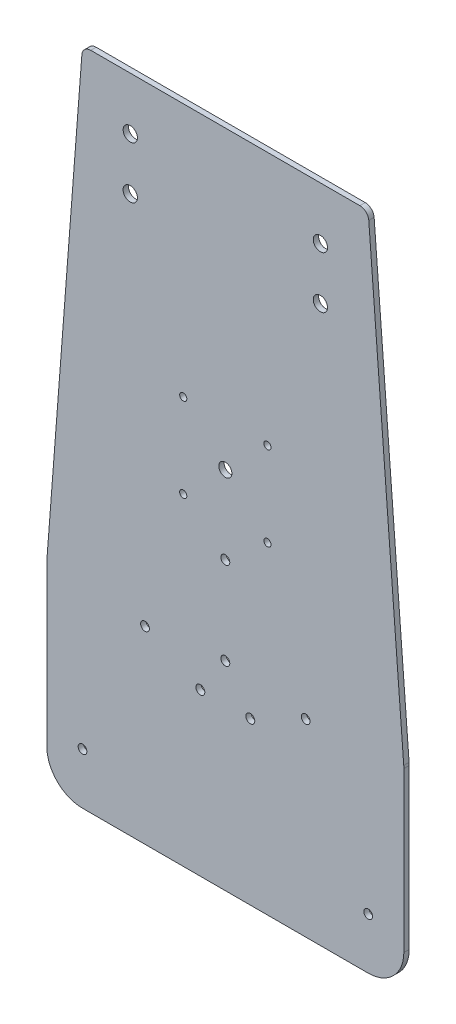
SolidWorks part; units mm, degrees
ref_plane "Alzado" through (0, 0, 0) normal (0, 0, 1) x (1, 0, 0)
ref_plane "Planta" through (0, 0, 0) normal (0, 1, 0) x (1, 0, 0)
ref_plane "Vista lateral" through (0, 0, 0) normal (1, 0, 0) x (0, 0, -1)
sketch "Croquis1" plane through (0, 0, 0) normal (0, 0, 1) x (1, 0, 0)
  line L0 (0, -28.2) -> (0, -108.2) construction
  line L1 (-23.57, -23.57) -> (23.57, -23.57) construction
  line L2 (-23.57, -23.57) -> (-23.57, 23.57) construction
  line L3 (-23.57, 23.57) -> (23.57, 23.57) construction
  line L4 (23.57, -23.57) -> (23.57, 23.57) construction
  line L5 (-23.57, -23.57) -> (23.57, 23.57) construction
  line L6 (-23.57, 23.57) -> (23.57, -23.57) construction
  line L7 (-28.2, -28.2) -> (28.2, -28.2) construction
  line L8 (-28.2, -28.2) -> (-28.2, 28.2) construction
  line L9 (-28.2, 28.2) -> (28.2, 28.2) construction
  line L10 (28.2, -28.2) -> (28.2, 28.2) construction
  line L11 (-28.2, -28.2) -> (28.2, 28.2) construction
  line L12 (-28.2, 28.2) -> (28.2, -28.2) construction
  line L13 (0, -28.2) -> (30.1, -28.2) construction
  line L14 (0, -108.2) -> (0, -169.2) construction
  line L15 (-30.1, -108.2) -> (30.1, -108.2) construction
  line L16 (-30.1, -108.2) -> (-30.1, -28.2) construction
  line L17 (-30.1, -28.2) -> (30.1, -28.2) construction
  line L18 (30.1, -108.2) -> (30.1, -28.2) construction
  line L19 (-30.1, -108.2) -> (30.1, -28.2) construction
  line L20 (-30.1, -28.2) -> (30.1, -108.2) construction
  line L21 (-14, -108.7) -> (-14, -113.7) construction
  line L22 (-221.5898, -108.7) -> (221.5898, -108.7) construction
  line L23 (-221.5898, -108.7) -> (-221.5898, -168.7) construction
  line L24 (-221.5898, -168.7) -> (221.5898, -168.7) construction
  line L25 (221.5898, -108.7) -> (221.5898, -168.7) construction
  line L26 (-221.5898, -108.7) -> (221.5898, -168.7) construction
  line L27 (-221.5898, -168.7) -> (221.5898, -108.7) construction
  line L28 (-221.5898, -122.2) -> (221.5898, -122.2) construction
  line L29 (-221.5898, -138.7) -> (221.5898, -138.7) construction
  line L30 (0, -169.2) -> (0, -204.2) construction
  line L31 (-100, -204.2) -> (100, -204.2)
  line L32 (100, -204.2) -> (100, -94.2)
  line L33 (100, -94.2) -> (80, 165.8)
  line L34 (80, 165.8) -> (-80, 165.8)
  line L35 (0, 165.8) -> (0, -169.2) construction
  line L36 (-100, -204.2) -> (-100, -94.2)
  line L37 (-100, -94.2) -> (-80, 165.8)
  line L38 (53.25, 121.8) -> (68.3, 121.8) construction
  line L39 (-53.25, 121.8) -> (-68.3, 121.8) construction
  line L40 (38.2, 91.75) -> (68.3, 91.75) construction
  line L41 (38.2, 91.75) -> (38.2, 151.85) construction
  line L42 (38.2, 151.85) -> (68.3, 151.85) construction
  line L43 (68.3, 91.75) -> (68.3, 151.85) construction
  line L44 (38.2, 91.75) -> (68.3, 151.85) construction
  line L45 (38.2, 151.85) -> (68.3, 91.75) construction
  line L46 (-38.2, 151.85) -> (-68.3, 91.75) construction
  line L47 (-38.2, 91.75) -> (-68.3, 151.85) construction
  line L48 (-38.2, 151.85) -> (-68.3, 151.85) construction
  line L49 (-38.2, 91.75) -> (-38.2, 151.85) construction
  line L50 (-38.2, 91.75) -> (-68.3, 91.75) construction
  line L51 (-68.3, 91.75) -> (-68.3, 151.85) construction
  circle A0 centre (-23.57, 23.57) radius 2
  circle A1 centre (23.57, 23.57) radius 2
  circle A2 centre (-23.57, -23.57) radius 2
  circle A3 centre (23.57, -23.57) radius 2
  circle A4 centre (0, 0) radius 3.675
  circle A5 centre (-14, -113.7) radius 6 construction
  circle A6 centre (14, -113.7) radius 6 construction
  circle A7 centre (-14, -113.7) radius 2.5
  circle A8 centre (14, -113.7) radius 2.5
  circle A9 centre (0, 0) radius 8 construction
  circle A10 centre (-45, -98.4) radius 12 construction
  circle A11 centre (-45, -98.4) radius 2.45
  circle A12 centre (45, -98.4) radius 12 construction
  circle A13 centre (45, -98.4) radius 2.45
  circle A14 centre (-80, -175.5) radius 12 construction
  circle A15 centre (-80, -175.5) radius 2.45
  circle A16 centre (80, -175.5) radius 2.45
  circle A17 centre (80, -175.5) radius 12 construction
  circle A18 centre (0, -43.7) radius 2.5
  circle A19 centre (0, -92.7) radius 2.5
  circle A20 centre (53.25, 136.35) radius 4
  circle A21 centre (53.25, 107.25) radius 4
  circle A22 centre (-53.25, 107.25) radius 4
  circle A23 centre (-53.25, 136.35) radius 4
  point P0 (0, 0)
  point P10 (0, 0)
  point P19 (0, -68.2)
  point P21 (0, -138.7)
  point P64 (53.25, 121.8)
  dimension "D3" = 4
  dimension "D4" = 4
  dimension "D5" = 4
  dimension "D6" = 4
  dimension "D9" = 7.35
  dimension "D16" = 12
  dimension "D17" = 5
  dimension "D18" = 16
  dimension "D19" = 10.3
  dimension "D20" = 24
  dimension "D22" = 4.9
  dimension "D24" = 24
  dimension "D25" = 4.9
  dimension "D32" = 5
  dimension "D33" = 5
  dimension "D41" = 8
  dimension "D1" = 47.14
  dimension "D2" = 47.14
  dimension "D7" = 56.4
  dimension "D8" = 56.4
  dimension "D10" = 80
  dimension "D11" = 30.1
  dimension "D12" = 61
  dimension "D13" = 13.5
  dimension "D14" = 14
  dimension "D15" = 5
  dimension "D21" = 45
  dimension "D23" = 6.8
  dimension "D26" = 80
  dimension "D27" = 100
  dimension "D28" = 35
  dimension "D29" = 110
  dimension "D30" = 80
  dimension "D31" = 370
  dimension "D34" = 15.5
  dimension "D35" = 15.5
  dimension "D36" = 25.05
  dimension "D37" = 60.1
  dimension "D38" = 30.1
  dimension "D39" = 15.5
  dimension "D40" = 15.05
  dimension "D42" = 150
extrude "Saliente-Extruir1" add sketch "Croquis1" along normal blind 3
fillet "Redondeo1" radius 20 2 edges at (-100, -204.2, 1.5) (100, -204.2, 1.5)
fillet "Redondeo2" radius 20 2 edges at (100, -94.2, 1.5) (-100, -94.2, 1.5)
fillet "Redondeo3" radius 5 2 edges at (80, 165.8, 1.5) (-80, 165.8, 1.5)
